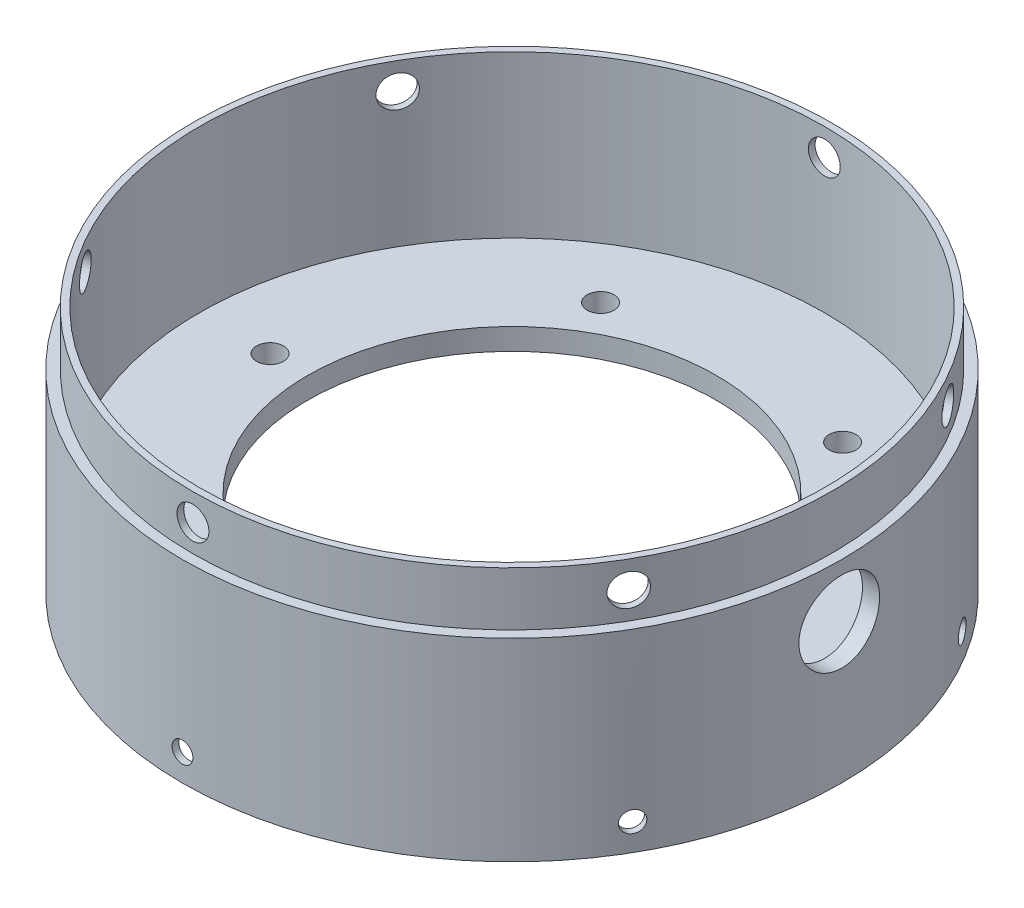
SolidWorks part; units mm, degrees
material "6061-T6 (SS)"
ref_plane "Front Plane" through (0, 0, 0) normal (0, 0, 1) x (1, 0, 0)
ref_plane "Top Plane" through (0, 0, 0) normal (0, 1, 0) x (1, 0, 0)
ref_plane "Right Plane" through (0, 0, 0) normal (1, 0, 0) x (0, 0, -1)
ref_axis "Axis1" through (0, 55, 0) along (0, -1, 0)
ref_plane "Plane1" through (0, 0, 0) normal (0.866, 0, 0.5) x (0, -1, 0)
sketch "Sketch3" plane through (0, 0, 0) normal (0, 1, 0) x (1, 0, 0)
  circle A0 centre (0, 0) radius 77.8637
  dimension "D1" = 155.7274
extrude "Boss-Extrude1" add sketch "Sketch3" along normal blind 2.54 and the other way blind 2.54
sketch "Sketch4" plane through (0, 2.54, 0) normal (0, 1, 0) x (1, 0, 0)
  circle A0 centre (0, 0) radius 77.8637
  circle A1 centre (0, 0) radius 73.8505
  dimension "D1" = 155.7274
  dimension "D2" = 147.701
extrude "Boss-Extrude3" add sketch "Sketch4" along normal blind 25.4
sketch "Sketch5" plane through (0, 27.94, 0) normal (0, 1, 0) x (1, 0, 0)
  circle A0 centre (0, 0) radius 73.8505
  circle A1 centre (0, 0) radius 73.8505 construction
  circle A2 centre (0, 0) radius 75.438
  dimension "D1" = 150.876
extrude "Boss-Extrude4" add sketch "Sketch5" along normal blind 12.7
hole_wizard "19/64 (0.29688) Diameter Hole1" positions "3DSketch1" profile "Sketch6" hole size "19/64" standard "ANSI Inch" end condition up to next
sketch3d "3DSketch1"
  point P0 (0, 34.29, 75.438)
  dimension "D1" = 6.35
sketch "Sketch6" plane through (0, 34.29, 75.438) normal (1, 0, 0) x (0, -1, 0)
  line L0 (0, 0) -> (0, 176.321)
  line L1 (0, 176.321) -> (3.7704, 176.321)
  line L2 (3.7704, 176.321) -> (3.7704, 0)
  line L5 (3.7704, 0) -> (0, 0)
  line L11 (0, -6.35) -> (0, 107.95) construction
  dimension "Thru Hole Dia." = 7.5408
  dimension "Thru Hole Depth" = 176.321
sketch "Sketch7" plane through (0, -2.54, 0) normal (0, -1, 0) x (1, 0, 0)
  circle A0 centre (0, 0) radius 73.8505
  circle A1 centre (0, 0) radius 77.8637
  circle A2 centre (0, 0) radius 77.8637 construction
  dimension "D1" = 147.701
extrude "Boss-Extrude5" add sketch "Sketch7" along normal blind 2.54
sketch "Sketch8" plane through (0, -5.08, 0) normal (0, -1, 0) x (1, 0, 0)
  circle A0 centre (0, 0) radius 76.2889
  circle A1 centre (0, 0) radius 77.8637
  circle A4 centre (0, 0) radius 77.8637 construction
  dimension "D1" = 152.5778
extrude "Boss-Extrude6" add sketch "Sketch8" along normal blind 12.7
hole_wizard "#10 (0.1935) Diameter Hole1" positions "3DSketch2" profile "Sketch9" hole size "#10" standard "ANSI Inch" end condition up to next
sketch3d "3DSketch2"
  point P0 (0, -11.43, 77.8637)
  dimension "D1" = 6.35
sketch "Sketch9" plane through (0, -11.43, 77.8637) normal (1, 0, 0) x (0, -1, 0)
  line L0 (0, 0) -> (0, 182.0776)
  line L1 (0, 182.0776) -> (2.4574, 182.0776)
  line L2 (2.4574, 182.0776) -> (2.4574, 0)
  line L5 (2.4574, 0) -> (0, 0)
  line L11 (0, -6.35) -> (0, 107.95) construction
  dimension "Thru Hole Dia." = 4.9149
  dimension "Thru Hole Depth" = 182.0776
hole_wizard "1/4 (0.25) Diameter Hole3" positions "Sketch11" profile "Sketch12" hole size "1/4" standard "ANSI Inch" end condition up to next
sketch "Sketch11" plane through (0, 2.54, 0) normal (0, 1, 0) x (1, 0, 0)
  line L0 (-30.25, -52.3945) -> (30.25, 52.3945) construction
  point P0 (-28.575, -49.4934)
  dimension "D1" = 57.15
sketch "Sketch12" plane through (-28.575, 2.54, 49.4934) normal (1, 0, 0) x (0, 0, 1)
  line L0 (0, 0) -> (0, 5.081)
  line L1 (0, 5.081) -> (3.175, 5.081)
  line L2 (3.175, 5.081) -> (3.175, 0)
  line L5 (3.175, 0) -> (0, 0)
  line L11 (0, -6.35) -> (0, 107.95) construction
  dimension "Thru Hole Dia." = 6.35
  dimension "Thru Hole Depth" = 5.081
pattern_circular "CirPattern2" count 6 over 360 about axis through (0, 55, 0) along (0, -1, 0) of "19/64 (0.29688) Diameter Hole1", "#10 (0.1935) Diameter Hole1", "1/4 (0.25) Diameter Hole3"
sketch "Sketch10" plane through (0, 2.54, 0) normal (0, 1, 0) x (1, 0, 0)
  circle A0 centre (0, 0) radius 48.26
  dimension "D1" = 96.52
extrude "Cut-Extrude2" cut sketch "Sketch10" against normal up to next
hole_wizard "3/4 (0.75) Diameter Hole1" positions "3DSketch3" profile "Sketch15" hole size "3/4" standard "ANSI Inch" end condition up to next
sketch3d "3DSketch3"
  point P0 (77.8637, 15.24, 0)
  dimension "D1" = 12.7
sketch "Sketch15" plane through (77.8637, 15.24, 0) normal (0, 1, 0) x (0, 0, -1)
  line L0 (0, 0) -> (0, 4.0132)
  line L1 (0, 4.0132) -> (9.525, 4.0132)
  line L2 (9.525, 4.0132) -> (9.525, 0)
  line L5 (9.525, 0) -> (0, 0)
  line L11 (0, -6.35) -> (0, 107.95) construction
  dimension "Thru Hole Dia." = 19.05
  dimension "Thru Hole Depth" = 4.0132
